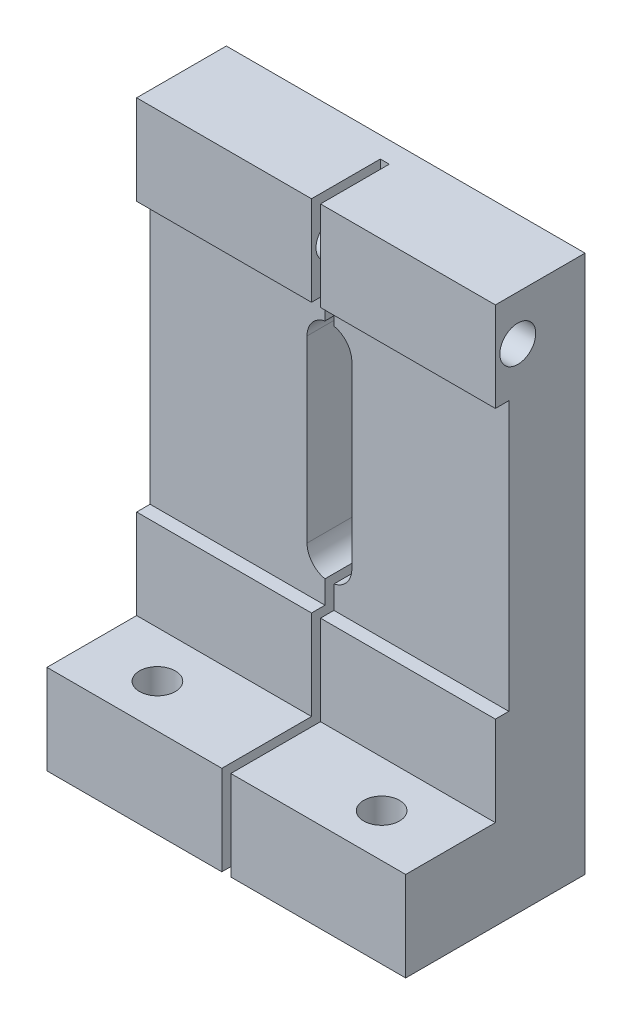
SolidWorks part; units mm, degrees
ref_plane "Front Plane" through (0, 0, 0) normal (0, 0, 1) x (1, 0, 0)
ref_plane "Top Plane" through (0, 0, 0) normal (0, 1, 0) x (1, 0, 0)
ref_plane "Right Plane" through (0, 0, 0) normal (1, 0, 0) x (0, 0, -1)
sketch "Sketch1" plane through (0, 0, 0) normal (0, 0, 1) x (1, 0, 0)
  line L1 (0, 0) -> (-40, 0)
  line L2 (0, 0) -> (0, -60)
  line L3 (0, -60) -> (-40, -60)
  line L4 (-40, 0) -> (-40, -60)
  dimension "D1" = 40
  dimension "D2" = 60
extrude "Boss-Extrude1" add sketch "Sketch1" along normal blind 10
sketch "Sketch2" plane through (0, 0, 10) normal (0, 0, 1) x (1, 0, 0)
  line L0 (-20, -15) -> (-20, -35) construction
  line L1 (-17.5, -15) -> (-17.5, -35)
  line L2 (-22.5, -15) -> (-22.5, -35)
  line L3 (0, -60) -> (0, 0) construction
  line L4 (-40, -60) -> (0, -60) construction
  arc A0 (-17.5, -15) -> (-22.5, -15) centre (-20, -15) ccw
  arc A1 (-22.5, -35) -> (-17.5, -35) centre (-20, -35) ccw
  point P2 (-20, -25)
  dimension "D1" = 5
  dimension "D2" = 20
  dimension "D3" = 20
  dimension "D4" = 35
extrude "Cut-Extrude1" cut sketch "Sketch2" against normal through all
sketch "Sketch5" plane through (0, 0, 0) normal (1, 0, 0) x (0, 0, -1)
  line L0 (-8.5, -10) -> (-10, -10)
  line L1 (-10, -60) -> (-10, 0) construction
  line L2 (-8.5, -10) -> (-8.5, -40)
  line L3 (-10, -60) -> (0, -60) construction
  line L4 (-8.5, -40) -> (-10, -40)
  line L7 (-10, -10) -> (-10, -40)
  dimension "D1" = 1.5
  dimension "D4" = 30
  dimension "D5" = 20
extrude "Cut-Extrude4" cut sketch "Sketch5" against normal through all
sketch "Sketch6" plane through (0, 0, 10) normal (0, 0, 1) x (1, 0, 0)
  line L0 (-40, -40) -> (-40, -60) construction
  line L1 (0, -60) -> (-40, -60)
  line L2 (0, -60) -> (0, -50)
  line L3 (0, -50) -> (-40, -50)
  line L4 (-40, -60) -> (-40, -50)
  dimension "D1" = 10
extrude "Boss-Extrude2" add sketch "Sketch6" along normal blind 10
sketch "Sketch7" plane through (0, -50, 0) normal (0, 1, 0) x (1, 0, 0)
  line L3 (-40, -20) -> (-40, -10) construction
  circle A0 centre (-7.5, -15.1829) radius 2
  circle A1 centre (-32.5, -15.1829) radius 2
  dimension "D1" = 4
  dimension "D2" = 4
  dimension "D3" = 7.5
  dimension "D5" = 25
extrude "Cut-Extrude5" cut sketch "Sketch7" against normal blind 40
sketch "Sketch8" plane through (0, 0, 0) normal (0, 1, 0) x (1, 0, 0)
  line L2 (-20.5, -20) -> (-19.5, -20)
  line L5 (-20.5, -20) -> (-20.5, -2.3294)
  line L7 (0, -20) -> (-40, -20) construction
  line L9 (-20.5, -2.3294) -> (-19.5, -2.3294)
  line L10 (-19.5, -20) -> (-19.5, -2.3294)
  line L11 (-22.5, 0) -> (-22.5, -8.5) construction
  dimension "D1" = 1
  dimension "D2" = 2
extrude "Cut-Extrude7" cut sketch "Sketch8" against normal up to surface (60 mm away) up to face at (-32.5, -60, 17.1829)
sketch "Sketch9" plane through (0, -60, 0) normal (0, -1, 0) x (1, 0, 0)
  line L3 (0, 20) -> (0, 0) construction
  line L5 (-40, 8.5) -> (-20.5, 8.5) construction
  circle A0 centre (-32.5, 6.5) radius 2
  circle A1 centre (-7.5, 6.5) radius 2
  dimension "D1" = 4
  dimension "D3" = 7.5
  dimension "D4" = 4
  dimension "D2" = 25
extrude "Cut-Extrude9" cut sketch "Sketch9" against normal blind 15
sketch "Sketch10" plane through (0, 0, 0) normal (1, 0, 0) x (0, 0, -1)
  line L1 (-10, 0) -> (0, 0) construction
  line L2 (-10, -10) -> (-10, 0) construction
  circle A0 centre (-7.5, -5) radius 2
  dimension "D1" = 4
  dimension "D2" = 5
  dimension "D3" = 2.5
extrude "Cut-Extrude10" cut sketch "Sketch10" against normal blind 30
